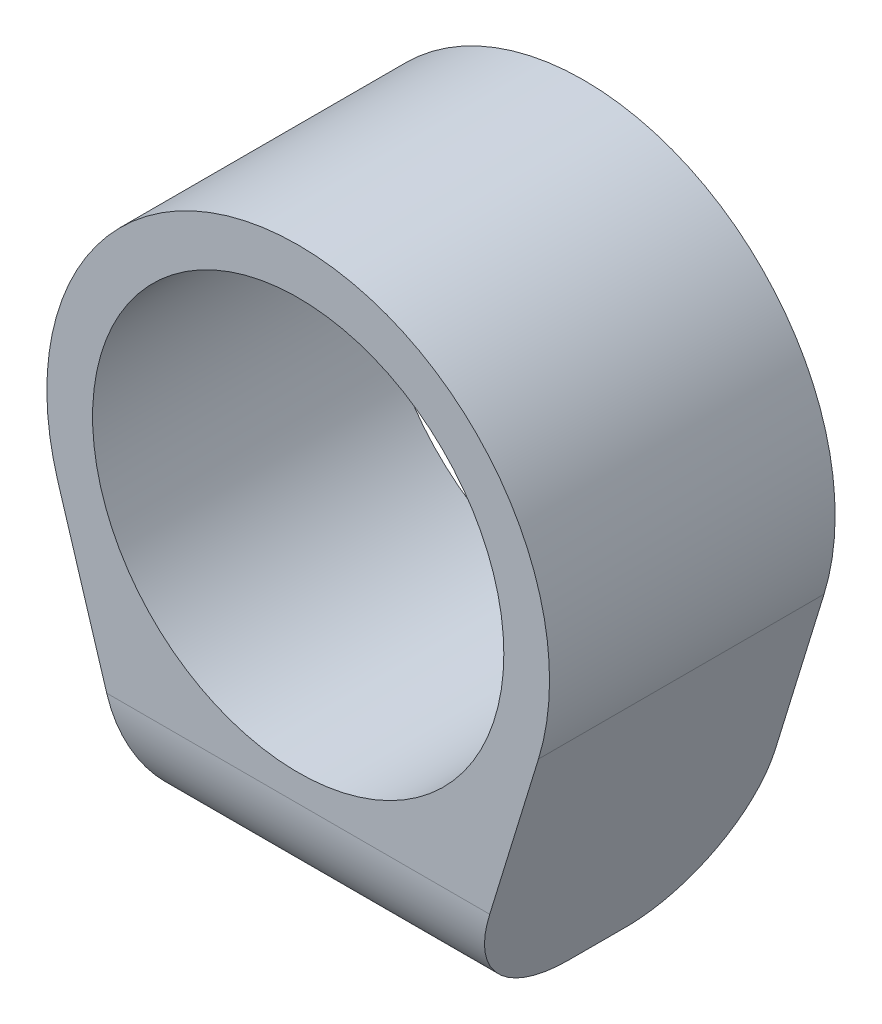
SolidWorks part; units mm, degrees
ref_plane "Ön Düzlem" through (0, 0, 0) normal (0, 0, 1) x (1, 0, 0)
ref_plane "Üst Düzlem" through (0, 0, 0) normal (0, 1, 0) x (1, 0, 0)
ref_plane "Sağ Düzlem" through (0, 0, 0) normal (1, 0, 0) x (0, 0, -1)
sketch "Sketch1" plane through (0, 0, 0) normal (0, 0, 1) x (1, 0, 0)
  line L0 (-21.0314, -6.456) -> (-13.695, -30.3553)
  line L1 (0, 0) -> (0, -30.8742) construction
  line L2 (21.0314, -6.456) -> (13.695, -30.3553)
  line L3 (-13.695, -30.3553) -> (13.695, -30.3553)
  circle A0 centre (0, 0) radius 18
  arc A1 (21.0314, -6.456) -> (-21.0314, -6.456) centre (0, 0) ccw
  dimension "D1" = 36
  dimension "D2" = 44
  dimension "D3" = 25
extrude "Boss-Extrude1" add sketch "Sketch1" along normal blind 25
sketch "Sketch2" plane through (0, -30.3553, 0) normal (0, -1, 0) x (1, 0, 0)
  line L0 (-13.695, 12.5) -> (13.695, 12.5) construction
  line L1 (-13.695, 25) -> (-13.695, 0) construction
  line L2 (13.695, 25) -> (13.695, 0) construction
  line L4 (-4.5, 12.5) -> (4.5, 12.5)
  line L5 (-13.695, 0) -> (13.695, 0) construction
  circle A0 centre (-4.5, 12.5) radius 2.5
  circle A1 centre (4.5, 12.5) radius 2.5
  point P10 (0, 12.5)
  point P13 (0, 0)
  dimension "D2" = 5
  dimension "D3" = 5
  dimension "D1" = 9
extrude "Cut-Extrude1" cut sketch "Sketch2" against normal blind 10 contours L0 A0 L4 | A0 L0 L4 | L0 L4 A1 | L4 L0 A1 region at (-4.5, -30.3553, 13.561) region at (-4.5, -30.3553, 11.439) region at (4.5, -30.3553, 13.561) region at (4.5, -30.3553, 11.439)
fillet "Fillet1" radius 10 2 edges at (0, -30.3553, 0) (0, -30.3553, 25)
